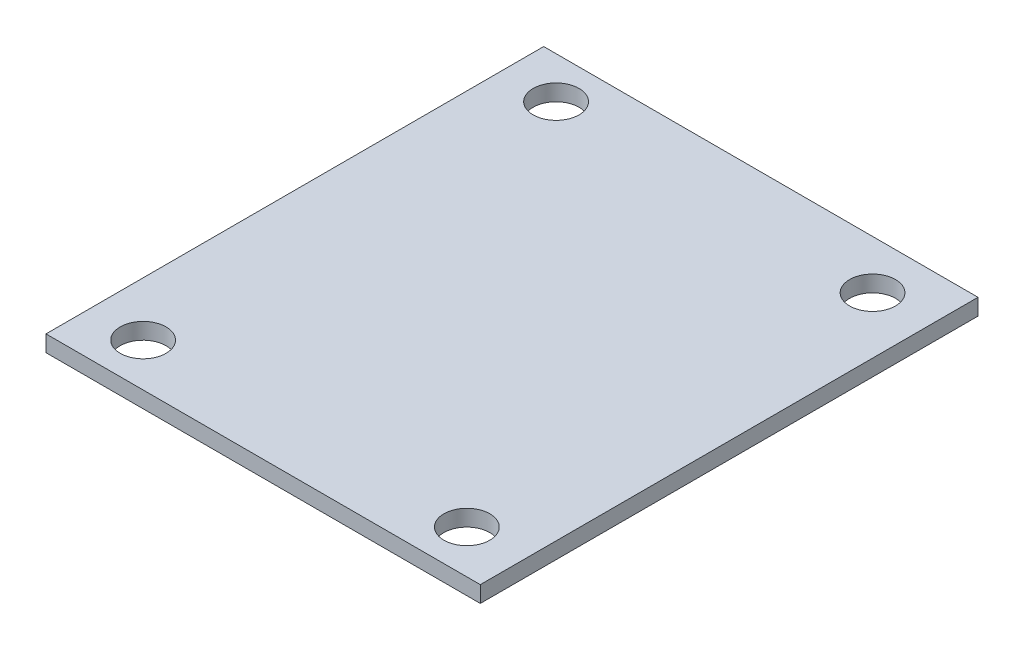
SolidWorks part; units mm, degrees
ref_plane "Front Plane" through (0, 0, 0) normal (0, 0, 1) x (1, 0, 0)
ref_plane "Top Plane" through (0, 0, 0) normal (0, 1, 0) x (1, 0, 0)
ref_plane "Right Plane" through (0, 0, 0) normal (1, 0, 0) x (0, 0, -1)
sketch "Sketch1" plane through (0, 0, 0) normal (0, 1, 0) x (1, 0, 0)
  line L1 (16.1, -18.45) -> (-16.1, -18.45)
  line L2 (16.1, -18.45) -> (16.1, 18.45)
  line L3 (16.1, 18.45) -> (-16.1, 18.45)
  line L4 (-16.1, -18.45) -> (-16.1, 18.45)
  line L5 (16.1, -18.45) -> (-16.1, 18.45) construction
  line L6 (16.1, 18.45) -> (-16.1, -18.45) construction
  point P0 (0, 0)
  dimension "D1" = 32.2
  dimension "D2" = 36.9
base flange "Base-Flange1" sketch "Sketch1" thickness 1.21 reverse thickness direction no parameters "D1"=0.762
sketch "Sketch6" plane through (0, 0, 0) normal (0, 1, 0) x (1, 0, 0)
  point P0 (0, 0)
hole_wizard "M3 Clearance Hole1" positions "Sketch10" profile "Sketch8" hole size "M3" standard "ANSI Metric"
sketch "Sketch10" plane through (0, -1.21, 0) normal (0, -1, 0) x (-1, 0, 0)
  line L0 (16.1, 18.45) -> (16.1, -18.45) construction
  point P0 (-11.9, -15.2483)
  point P2 (12.1, -15.2483)
  point P4 (12.1, 15.3709)
  point P6 (-11.9, 14.8325)
  dimension "D1" = 24
  dimension "D2" = 24
  dimension "D3" = 4
  dimension "D4" = 4
sketch "Sketch8" plane through (11.9, -1.21, 15.2483) normal (1, 0, 0) x (0, 0, -1)
  line L0 (0, 0) -> (0, 4.3615)
  line L1 (0, 4.3615) -> (1.7, 3.34)
  line L2 (1.7, 3.34) -> (1.7, 0)
  line L5 (1.7, 0) -> (0, 0)
  line L10 (0, 4.3615) -> (-1.7, 3.34) construction
  line L11 (0, -6.35) -> (0, 107.95) construction
  dimension "Hole Dia." = 3.4
  dimension "Hole Depth" = 3.34
  dimension "Drill Angle" = 118
sketch "Bend-Lines1" plane through (0, 0, 0) normal (0, 1, 0) x (1, 0, 0)
sketch "Bounding-Box1" plane through (0, 0, 0) normal (0, 1, 0) x (1, 0, 0)
sheet metal parameters "Sheet-Metal(1)" thickness 1.21 parameters "D1"=0.762
flat pattern "Flat-Pattern(1)" [suppressed]
sketch "Bend-Lines2" plane through (0, 0, 0) normal (0, 1, 0) x (1, 0, 0)
sketch "Bounding-Box2" [suppressed] plane through (0, 0, 0) normal (0, 1, 0) x (1, 0, 0)
sheet metal parameters "Sheet-Metal(2)" thickness 1.21 parameters "D1"=0.762
flat pattern "Flat-Pattern(1)"
sketch "Bend-Lines2" plane through (0, 0, 0) normal (0, 1, 0) x (1, 0, 0)
sketch "Bounding-Box2" [suppressed] plane through (0, 0, 0) normal (0, 1, 0) x (1, 0, 0)
